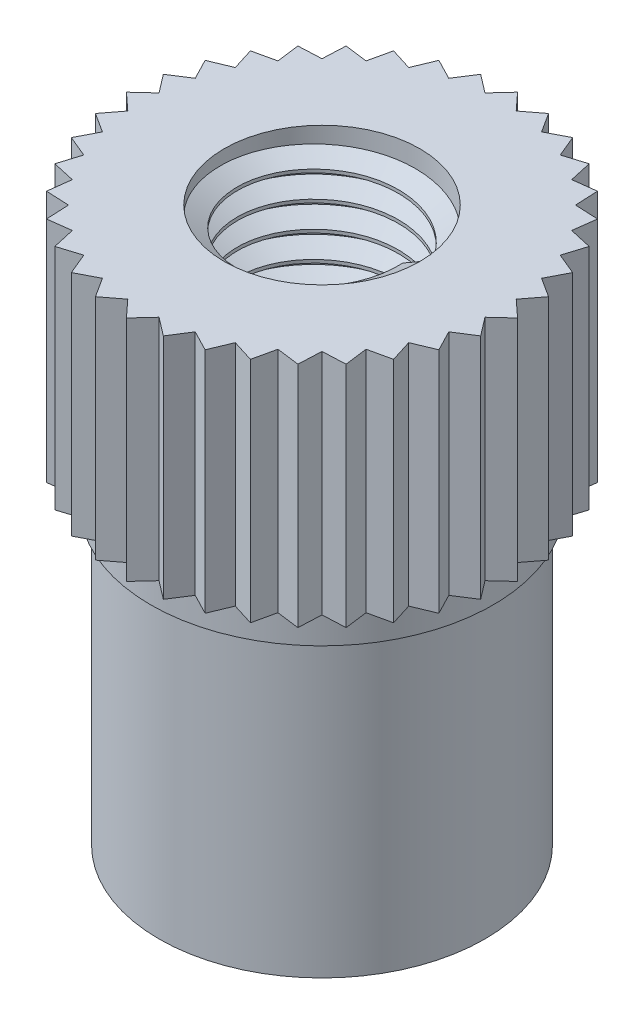
SolidWorks part; units mm, degrees
ref_plane "Alzado" through (0, 0, 0) normal (0, 0, 1) x (1, 0, 0)
ref_plane "Planta" through (0, 0, 0) normal (0, 1, 0) x (1, 0, 0)
ref_plane "Vista lateral" through (0, 0, 0) normal (1, 0, 0) x (0, 0, -1)
sketch "Croquis2" plane through (0, 0, 0) normal (0, 1, 0) x (1, 0, 0)
  circle A0 centre (0, 0) radius 3
  circle A1 centre (0, 0) radius 2.5
  circle A2 centre (0, 0) radius 1.5
  dimension "D1" = 6
  dimension "D2" = 5
  dimension "D3" = 3
extrude "Saliente-Extruir1" add sketch "Croquis2" along normal blind 8.5 contours A0
extrude "Cortar-Extruir1" cut sketch "Croquis2<3>" along normal blind 5 contours A0 A1 | A2 region at (-2.9151, 0, 0) region at (0, 0, 0)
sketch "Croquis2<3>" plane through (0, 0, 0) normal (0, 1, 0) x (1, 0, 0) same geometry as "Croquis2"
sketch "Croquis4" plane through (0, 8.5, 0) normal (0, 1, 0) x (1, 0, 0)
  line L0 (0, 0) -> (-3, 0)
  line L1 (0, 0) -> (-4.8666, 0.4258)
  line L2 (0, 0) -> (-4.6376, 0.8177)
  line L3 (-2.7395, 0.2397) -> (-3, 0)
  line L4 (-2.7395, 0.2397) -> (-2.9544, 0.5209)
  circle A0 centre (0, 0) radius 2.75
  circle A1 centre (0, 0) radius 3 construction
  circle A2 centre (0, 0) radius 3
  point P8 (-2.9544, 0.5209)
  dimension "D1" = 5.5
  dimension "D2" = 5
  dimension "D3" = 10
extrude "Cortar-Extruir3" cut sketch "Croquis4" against normal through all contours L3 L1 | L1 L4 L3 region at (-2.9107, 8.5, -0.1665) region at (-2.8954, 8.5, -0.3415)
pattern_circular "MatrizC2" count 37 every 10 about axis through (0, 5, 0) along (0, -1, 0) of "Cortar-Extruir3"
sketch "Croquis5" plane through (0, 5, 0) normal (0, -1, 0) x (1, 0, 0)
  circle A0 centre (0, 0) radius 2.625
  dimension "D1" = 5.25
extrude "Saliente-Extruir2" add sketch "Croquis5" along normal blind 0.5
hole_wizard "Perforador para roscar para macho de roscar para M21" positions "Croquis7" profile "Croquis9" hole size "M2" standard "ISO"
sketch "Croquis7" plane through (0, 8.5, 0) normal (0, 1, 0) x (1, 0, 0)
  point P0 (0, 0)
sketch "Croquis9" plane through (0, 8.5, 0) normal (1, 0, 0) x (0, 0, 1)
  line L0 (0, 0) -> (0, 3)
  line L1 (0, 3) -> (1.5, 3)
  line L2 (1.5, 3) -> (1.5, 0)
  line L5 (1.5, 0) -> (0, 0)
  line L10 (0, 3) -> (-1.5, 3) construction
  line L11 (0, -6.35) -> (0, 107.95) construction
  dimension "Diámetro de taladro" = 3
  dimension "Profundidad de taladro" = 3
  dimension "Ángulo de perforador" = 180
sketch "Croquis13" plane through (0, 8.5, 0) normal (0, 1, 0) x (1, 0, 0)
  circle A0 centre (0, 0) radius 1.5
  circle A1 centre (0, 0) radius 1.5 construction
curve "Hélice/Espiral1" pitch 0.4 height 3 radius 1.5 centre (0, 8.5, 0) axis (0, -1, 0) start towards (1, 0, 0)
sketch "Croquis16" plane through (0, 0, 0) normal (0, 0, 1) x (1, 0, 0)
  line L0 (0, 0) -> (0, 8.5)
  line L1 (0, 8.5) -> (1.5, 8.5)
  line L2 (1.5, 8.5) -> (-1.5, 8.5) construction
  line L3 (1.5, 8.5) -> (1.2402, 8.35)
  line L4 (1.2402, 8.35) -> (1.2402, 8.3)
  line L5 (1.2402, 8.3) -> (1.5, 8.15)
  line L6 (1.5, 8.5) -> (1.5, 8.15)
  line L7 (1.5, 8.325) -> (1.2402, 8.325) construction
  line L8 (1.3701, 8.425) -> (1.3701, 8.225) construction
sweep "Barrer1" add profiles "Croquis16" path "Hélice/Espiral1"
